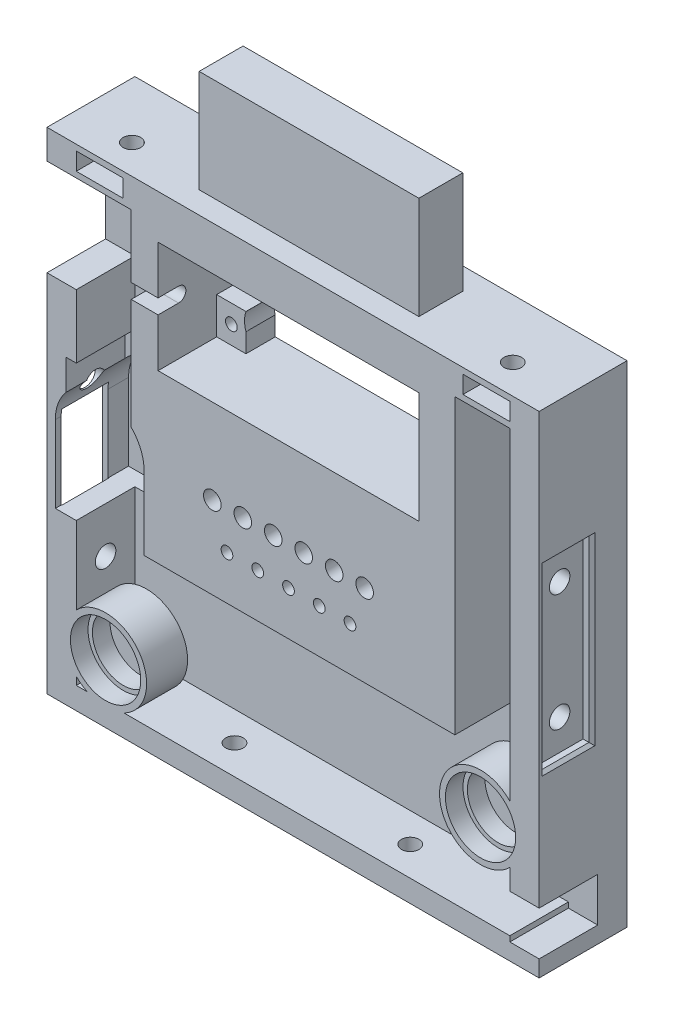
SolidWorks part; units mm, degrees
ref_plane "Front Plane" through (0, 0, 0) normal (0, 0, 1) x (1, 0, 0)
ref_plane "Top Plane" through (0, 0, 0) normal (0, 1, 0) x (1, 0, 0)
ref_plane "Right Plane" through (0, 0, 0) normal (1, 0, 0) x (0, 0, -1)
sketch "Sketch1" plane through (0, 0, 0) normal (0, 0, 1) x (1, 0, 0)
  line L1 (167.1854, 6.9235) -> (167.1854, 193.7719)
  line L2 (167.1854, 193.7719) -> (-0.8146, 193.7719)
  line L3 (-0.8146, 193.7719) -> (-0.8146, 6.9235)
  line L5 (81.6254, 98.7719) -> (102.6254, 98.7719) construction
  line L6 (83.1854, 270.7719) -> (99.1854, 270.7719) construction
  circle A0 centre (81.6254, 98.7719) radius 2
  circle A1 centre (102.6254, 98.7719) radius 2
  circle A2 centre (92.1254, 98.7719) radius 2
  circle A3 centre (60.6254, 98.7719) radius 2
  circle A4 centre (71.1254, 98.7719) radius 2
  arc A5 (83.1854, -1.2281) -> (167.1854, 6.9235) centre (99.1854, 270.7719) ccw
  arc A6 (83.1854, -1.2281) -> (-0.8146, 6.9235) centre (67.1854, 270.7719) cw
  dimension "D3" = 4
  dimension "D4" = 4
  dimension "D5" = 4
  dimension "D2" = 10.5
  dimension "D6" = 21
  dimension "D7" = 95
  dimension "D8" = 10.5
  dimension "D9" = 10.5
  dimension "D10" = 16
  dimension "D11" = 168
  dimension "D12" = 10.5
  dimension "D13" = 195
  dimension "D14" = 82.44
extrude "Boss-Extrude1" add sketch "Sketch1" along normal blind 30
sketch "Sketch2" plane through (0, 0, 30) normal (0, 0, 1) x (1, 0, 0)
  line L0 (107.1254, 178.7719) -> (56.1254, 178.7719)
  line L1 (81.6254, 58.2567) -> (81.6254, 96.2567) construction
  line L2 (56.1254, 140.7719) -> (107.1254, 140.7719)
  line L3 (-0.8146, 193.7719) -> (-0.8146, 6.9235) construction
  line L4 (167.1854, 193.7719) -> (-0.8146, 193.7719) construction
  line L10 (116.6254, 159.7719) -> (121.1254, 159.7719) construction
  line L12 (56.1254, 178.7719) -> (56.1254, 169.2719) construction
  line L13 (56.1254, 169.2719) -> (46.6254, 169.2719) construction
  line L14 (56.1254, 159.7719) -> (72.2173, 159.7719) construction
  line L15 (42.1254, 159.7719) -> (42.1254, 172.5219) construction
  line L16 (81.6254, 178.7719) -> (81.6254, 140.7719) construction
  circle A0 centre (42.1254, 172.5219) radius 2
  circle A1 centre (121.1254, 159.7719) radius 2
  circle A2 centre (42.1254, 159.7719) radius 2
  arc A4 (56.1254, 140.7719) -> (56.1254, 159.7719) centre (56.1254, 150.2719) cw
  arc A5 (107.1254, 178.7719) -> (107.1254, 159.7719) centre (107.1254, 169.2719) cw
  arc A6 (107.1254, 140.7719) -> (107.1254, 159.7719) centre (107.1254, 150.2719) ccw
  arc A7 (56.1254, 178.7719) -> (56.1254, 159.7719) centre (56.1254, 169.2719) ccw
  circle A8 centre (42.1254, 147.0219) radius 2
  circle A9 centre (121.1254, 147.0219) radius 2
  circle A10 centre (121.1254, 172.5219) radius 2
  dimension "D6" = 4
  dimension "D11" = 39.5
  dimension "D1" = 0
  dimension "D2" = 38
  dimension "D3" = 82.44
  dimension "D4" = 51
  dimension "D5" = 4.5
  dimension "D7" = 15
  dimension "D8" = 9.5
  dimension "D9" = 9.5
  dimension "D10" = 12.75
extrude "Cut-Extrude1" cut sketch "Sketch2" against normal through all both and the other way through all
sketch "Sketch3" plane through (0, 193.7719, 0) normal (0, 1, 0) x (1, 0, 0)
  line L0 (83.1854, 0) -> (83.1854, -7.5) construction
  line L1 (-0.8146, -30) -> (-0.8146, 0) construction
  line L3 (167.1854, 0) -> (-0.8146, 0) construction
  line L4 (83.1854, -7.5) -> (118.6254, -7.5) construction
  line L5 (118.6254, -7.5) -> (118.6254, -22.5) construction
  line L6 (118.6254, -22.5) -> (43.6254, -22.5) construction
  line L7 (43.6254, -22.5) -> (43.6254, -7.5) construction
  line L8 (43.6254, -7.5) -> (83.1854, -7.5) construction
  line L9 (118.6254, -7.5) -> (43.6254, -7.5)
  line L10 (43.6254, -7.5) -> (43.6254, -22.5)
  line L11 (43.6254, -22.5) -> (118.6254, -22.5)
  line L12 (118.6254, -22.5) -> (118.6254, -7.5)
  dimension "D1" = 75
  dimension "D2" = 44.44
  dimension "D3" = 7.5
extrude "Boss-Extrude2" add sketch "Sketch3" along normal blind 35
sketch "Sketch5" plane through (0, 0, 0) normal (0, 0, -1) x (-1, 0, 0)
  circle A0 centre (-42.1254, 159.7719) radius 4.375
  circle A1 centre (-121.1254, 159.7719) radius 4.375
  dimension "D1" = 8.75
  dimension "D2" = 8.75
extrude "Cut-Extrude4" cut sketch "Sketch5" against normal blind 2
sketch "Sketch6" plane through (0, 0, 0) normal (0, 0, -1) x (-1, 0, 0)
  line L0 (-60.6254, 98.7719) -> (-60.6254, 111.7719) construction
  line L1 (-60.6254, 111.7719) -> (0.8146, 111.7719) construction
  line L2 (0.8146, 193.7719) -> (0.8146, 6.9235) construction
  line L4 (0.8146, 111.7719) -> (-55.6254, 111.7719) construction
  line L5 (-167.1854, 6.9235) -> (-167.1854, 193.7719) construction
  circle A0 centre (-55.6254, 111.7719) radius 3
  circle A1 centre (-66.0254, 111.7719) radius 3
  circle A2 centre (-76.4254, 111.7719) radius 3
  circle A3 centre (-86.8254, 111.7719) radius 3
  circle A4 centre (-97.2254, 111.7719) radius 3
  circle A5 centre (-107.6254, 111.7719) radius 3
  dimension "D3" = 6
  dimension "D5" = 6
  dimension "D2" = 5
  dimension "D4" = 59.56
  dimension "D6" = 13
  dimension "D7" = 52
extrude "Cut-Extrude5" cut sketch "Sketch6" against normal through all
sketch "Sketch7" plane through (0, 0, 30) normal (0, 0, 1) x (1, 0, 0)
  line L0 (46.6254, 169.2719) -> (46.9367, 169.2719) construction
  line L6 (81.6254, 183.7719) -> (81.6254, 145.7719) construction
  line L8 (-0.8146, 193.7719) -> (-0.8146, 6.9235) construction
  line L15 (57.6854, 159.7719) -> (37.1047, 159.7719) construction
  line L17 (37.1047, 166.2719) -> (37.1047, 159.7719)
  line L18 (47.1047, 166.2719) -> (37.1047, 166.2719)
  line L22 (37.1047, 159.7719) -> (37.1047, 153.2719)
  line L24 (47.1047, 166.2719) -> (47.1047, 178.7719)
  line L25 (47.1047, 178.7719) -> (116.1461, 178.7719)
  line L27 (46.6254, 150.2719) -> (46.9367, 150.2719) construction
  line L29 (47.1047, 140.7719) -> (116.1461, 140.7719)
  line L30 (47.1047, 153.2719) -> (47.1047, 140.7719)
  line L31 (47.1047, 153.2719) -> (37.1047, 153.2719)
  line L32 (116.6254, 150.2719) -> (116.3141, 150.2719) construction
  line L33 (105.5654, 159.7719) -> (126.1461, 159.7719) construction
  line L34 (116.6254, 169.2719) -> (116.3141, 169.2719) construction
  line L35 (116.1461, 153.2719) -> (126.1461, 153.2719)
  line L36 (116.1461, 153.2719) -> (116.1461, 140.7719)
  line L39 (116.1461, 166.2719) -> (116.1461, 178.7719)
  line L40 (126.1461, 159.7719) -> (126.1461, 153.2719)
  line L41 (116.1461, 166.2719) -> (126.1461, 166.2719)
  line L42 (126.1461, 166.2719) -> (126.1461, 159.7719)
  line L43 (107.1254, 178.7719) -> (56.1254, 178.7719) construction
  line L44 (56.1254, 140.7719) -> (107.1254, 140.7719) construction
  arc A0 (56.1254, 178.7719) -> (56.1254, 159.7719) centre (56.1254, 169.2719) ccw construction
  point P33 (81.6254, 140.7719)
  point P35 (81.6254, 178.7719)
  dimension "D1" = 0
  dimension "D2" = 0
  dimension "D3" = 0
  dimension "D4" = 82.44
  dimension "D6" = 10
  dimension "D7" = 6.5
extrude "Cut-Extrude6" cut sketch "Sketch7" against normal through all and the other way through all
ref_plane "Plane1" through (0, 159.7719, 0) normal (0, 1, 0) x (1, 0, 0)
ref_plane "Plane2" through (81.6254, 0, 0) normal (-1, 0, 0) x (0, 0, 1)
mirror "Mirror2" about plane through (81.6254, 0, 0) normal (-1, 0, 0) rebuild error yes
sketch "Sketch9" plane through (167.1854, 0, 0) normal (1, 0, 0) x (0, 0, -1)
  line L1 (-30, 6.9235) -> (0, 6.9235) construction
  line L7 (-30, 6.9235) -> (-30, 193.7719) construction
  circle A0 centre (-20, 136.9235) radius 3.5
  circle A1 centre (-20, 96.9235) radius 3.5
  dimension "D5" = 40
  dimension "D6" = 10
  dimension "D7" = 90
sketch "Sketch10" plane through (-0.8146, 0, 0) normal (-1, 0, 0) x (0, 0, 1)
  line L0 (30, 6.9235) -> (0, 6.9235) construction
  line L7 (30, 193.7719) -> (30, 6.9235) construction
  circle A0 centre (20, 116.9235) radius 3.5
  circle A1 centre (20, 66.9235) radius 3.5
  dimension "D5" = 10
  dimension "D6" = 50
  dimension "D1" = 60
sketch "Sketch11" plane through (0, 0, 30) normal (0, 0, 1) x (1, 0, 0)
  line L0 (37.1047, 159.7719) -> (-0.8146, 159.7719) construction
  line L1 (37.1047, 153.2719) -> (37.1047, 166.2719) construction
  line L2 (-0.8146, 193.7719) -> (-0.8146, 6.9235) construction
  line L3 (-0.8146, 159.7719) -> (9.1854, 159.7719) construction
  line L4 (9.1854, 159.7719) -> (27.9354, 159.7719) construction
  line L14 (167.1854, 159.7719) -> (157.1854, 159.7719) construction
  line L15 (128.4341, 159.7719) -> (138.4354, 159.7719) construction
  line L21 (47.1047, 140.7719) -> (27.9354, 140.7719) construction
  line L22 (27.9354, 140.7719) -> (27.9354, 128.6081) construction
  line L24 (27.9354, 128.6081) -> (27.9354, 83.7719)
  line L30 (167.1854, 6.9235) -> (167.1854, 46.9235) construction
  line L31 (27.9354, 183.7719) -> (27.9354, 128.6081)
  line L32 (39.2538, 83.7719) -> (138.4354, 83.7719)
  line L33 (157.1854, 183.7719) -> (9.1854, 183.7719)
  line L34 (9.1854, 183.7719) -> (9.1854, 14.7903)
  line L35 (157.1854, 14.7903) -> (157.1854, 183.7719)
  line L37 (9.1854, 183.7719) -> (9.1854, 128.6081)
  line L38 (157.1854, 14.7903) -> (157.1854, 18.7719)
  line L40 (27.9354, 183.7719) -> (9.1854, 183.7719)
  line L41 (167.1854, 6.9235) -> (167.1854, 193.7719) construction
  line L42 (167.1854, 46.9235) -> (157.1854, 46.9235) construction
  line L47 (138.4354, 183.7719) -> (138.4354, 159.7719)
  line L48 (157.1854, 183.7719) -> (157.1854, 159.7719)
  line L51 (157.1854, 159.7719) -> (167.1854, 159.7719) construction
  line L52 (138.4354, 183.7719) -> (157.1854, 183.7719)
  line L53 (9.1854, 128.6081) -> (9.1854, 33.7719)
  line L54 (9.1854, 14.7903) -> (27.9354, 11.2531)
  line L55 (138.4354, 159.7719) -> (138.4354, 83.7719)
  line L56 (157.1854, 159.7719) -> (157.1854, 46.9235)
  line L57 (27.9354, 83.7719) -> (39.2538, 83.7719)
  line L58 (9.1854, 18.7719) -> (157.1854, 18.7719)
  line L60 (157.1854, 33.7719) -> (9.1854, 33.7719)
  line L62 (43.6254, 228.7719) -> (118.6254, 228.7719) construction
  line L63 (9.1854, 18.7719) -> (9.1854, 14.7903)
  line L64 (157.1854, 33.7719) -> (157.1854, 46.9235)
  arc A8 (9.1854, 14.7903) -> (83.1854, 8.7899) centre (67.1854, 270.7719) ccw
  arc A9 (83.1854, 8.7899) -> (157.1854, 14.7903) centre (99.1854, 270.7719) ccw
  arc A10 (27.9354, 11.2531) -> (83.1854, 8.7899) centre (67.1854, 270.7719) ccw
  arc A11 (83.1854, 8.7899) -> (157.1854, 14.7903) centre (99.1854, 270.7719) ccw
  dimension "D1" = 10
  dimension "D2" = 210
  dimension "D3" = 15
  dimension "D4" = 50
extrude "Cut-Extrude8" cut sketch "Sketch11" against normal blind 20
sketch "Sketch19" plane through (0, 14.7903, 0) normal (0, 1, 0) x (0, 0, 1)
  line L0 (30, 9.1854) -> (20, 9.1854) construction
  line L1 (10, 9.1854) -> (30, 9.1854) construction
  line L2 (20, 9.1854) -> (20, 19.1854) construction
  line L4 (20, 19.1854) -> (20, 16.4354)
  line L7 (20, 16.4354) -> (17, 16.4354)
  line L8 (17, 16.4354) -> (17, 21.9354)
  line L9 (17, 21.9354) -> (20, 21.9354)
  line L10 (20, 21.9354) -> (20, 19.1854)
  dimension "D1" = 3
  dimension "D2" = 2.75
  dimension "D3" = 5.5
  dimension "D4" = 10
extrude "Cut-Extrude12" cut sketch "Sketch19" against normal blind 10.5
fillet "Fillet2" radius 7 2 edges at (40.8679, -0.4243, 0) (125.503, -0.4243, 0)
sketch "Sketch20" plane through (9.1854, 0, 0) normal (1, 0, 0) x (0, 0, -1)
  line L0 (-30, 183.7719) -> (-30, 150.7719)
  line L1 (-30, 183.7719) -> (-30, 33.7719) construction
  line L2 (-30, 150.7719) -> (-10, 150.7719)
  line L3 (-10, 183.7719) -> (-10, 33.7719) construction
  line L4 (-10, 150.7719) -> (-10, 183.7719)
  line L5 (-10, 183.7719) -> (-30, 183.7719)
extrude "Cut-Extrude13" cut sketch "Sketch20" against normal blind 10
ref_plane "Plane5" through (0, 0, 15) normal (0, 0, 1) x (1, 0, 0)
extrude "Cut-Extrude14" cut sketch "Sketch10" against normal blind 20
sketch "Sketch21" plane through (0, 0, 10) normal (0, 0, 1) x (1, 0, 0)
  line L0 (-0.8146, 150.7719) -> (-0.8146, 183.7719) construction
  line L3 (167.1854, 193.7719) -> (-0.8146, 193.7719) construction
  circle A0 centre (17.1854, 108.7719) radius 4.75
  dimension "D1" = 18
  dimension "D2" = 85
extrude "Cut-Extrude15" cut sketch "Sketch21" against normal blind 20
sketch "Sketch22" plane through (0, 0, 10) normal (0, 0, 1) x (1, 0, 0)
  line L0 (2.0278, 108.7719) -> (2.0278, 82.5219)
  line L1 (2.0278, 82.5219) -> (32.343, 82.5219)
  line L2 (32.343, 82.5219) -> (32.343, 108.7719)
  arc A0 (32.343, 108.7719) -> (2.0278, 108.7719) centre (17.1854, 108.7719) ccw
  dimension "D1" = 26.25
extrude "Cut-Extrude16" cut sketch "Sketch22" against normal blind 5
sketch "Sketch25" plane through (37.1047, 0, 0) normal (1, 0, 0) x (0, 0, -1)
  line L0 (-30, 153.2719) -> (-30, 159.7719) construction
  line L1 (-30, 153.2719) -> (-30, 166.2719) construction
  line L2 (-30, 159.7719) -> (-23, 159.7719) construction
  line L3 (-23, 157.2719) -> (-30, 157.2719)
  line L4 (-30, 157.2719) -> (-30, 162.2719)
  line L5 (-30, 162.2719) -> (-23, 162.2719)
  arc A0 (-23, 157.2719) -> (-23, 162.2719) centre (-23, 159.7719) ccw
extrude "Cut-Extrude19" cut sketch "Sketch25" against normal blind 15
extrude "Cut-Extrude20" cut sketch "Sketch9" against normal blind 25
sketch "Sketch26" plane through (157.1854, 0, 0) normal (-1, 0, 0) x (0, 0, 1)
  line L0 (30, 46.9235) -> (10, 46.9235)
  line L1 (10, 46.9235) -> (10, 31.9235)
  line L2 (10, 14.7903) -> (10, 18.7719) construction
  line L3 (10, 31.9235) -> (30, 31.9235)
  line L4 (30, 14.7903) -> (30, 18.7719) construction
  line L5 (30, 31.9235) -> (30, 46.9235)
  dimension "D1" = 15
extrude "Cut-Extrude21" cut sketch "Sketch26" against normal blind 25
ref_plane "Plane4" through (83.1854, 0, 0) normal (-1, 0, 0) x (0, 0, 1)
mirror "Mirror9" about plane through (83.1854, 0, 0) normal (-1, 0, 0) of "Cut-Extrude12"
ref_plane "Plane6" through (0, -1.2281, 0) normal (0, -1, 0) x (-1, 0, 0)
sketch "Sketch27" plane through (0, -1.2281, 0) normal (0, -1, 0) x (-1, 0, 0)
  line L0 (-83.1854, -30) -> (-83.1854, -20) construction
  line L1 (-83.1854, -30) -> (-83.1854, -7) construction
  circle A0 centre (-83.1854, -20) radius 6.5
extrude "Cut-Extrude23" cut sketch "Sketch27" along normal blind 2
sketch "Sketch28" plane through (0, -1.2281, 0) normal (0, -1, 0) x (1, 0, 0)
  line L0 (83.1854, 26.5) -> (83.1854, 13.5) construction
  circle A0 centre (83.1854, 20) radius 6.5
extrude "Cut-Extrude24" cut sketch "Sketch28" against normal blind 2
sketch "Sketch30" plane through (0, 0.7719, 0) normal (0, -1, 0) x (1, 0, 0)
  circle A0 centre (83.1854, 20) radius 2
extrude "Cut-Extrude25" cut sketch "Sketch30" against normal up to next
sketch "Sketch31" plane through (0, 33.7719, 0) normal (0, 1, 0) x (1, 0, 0)
  line L0 (83.1854, -30) -> (83.1854, -10) construction
  line L1 (9.1854, -30) -> (157.1854, -30) construction
  line L2 (9.1854, -10) -> (157.1854, -10) construction
  line L3 (83.1854, -10) -> (83.1854, -20) construction
  line L4 (83.1854, -20) -> (113.1854, -20) construction
  line L5 (113.1854, -20) -> (53.1854, -20) construction
  circle A0 centre (53.1854, -20) radius 3
  circle A1 centre (113.1854, -20) radius 3
  dimension "D1" = 30
  dimension "D2" = 60
extrude "Cut-Extrude26" cut sketch "Sketch31" against normal blind 15
sketch "Sketch32" plane through (0, 0, 30) normal (0, 0, 1) x (1, 0, 0)
  line L0 (83.1854, 33.7719) -> (83.1854, 26.2719) construction
  line L1 (9.1854, 33.7719) -> (157.1854, 33.7719) construction
  line L2 (83.1854, 26.2719) -> (-8.5825, 26.2719)
  line L3 (-8.5825, 26.2719) -> (-8.5825, -8.8315)
  line L4 (-8.5825, -8.8315) -> (175.9833, -8.8315)
  line L5 (175.9833, -8.8315) -> (175.9833, 26.2719)
  line L6 (175.9833, 26.2719) -> (83.1854, 26.2719)
extrude "Cut-Extrude27" cut sketch "Sketch32" against normal blind 30
sketch "Sketch33" plane through (167.1854, 0, 0) normal (1, 0, 0) x (0, 0, -1)
  line L0 (-20, 136.9235) -> (-20, 147.4235) construction
  line L1 (-20, 147.4235) -> (-12, 147.4235) construction
  line L2 (-20, 96.9235) -> (-20, 86.4235) construction
  line L3 (-20, 86.4235) -> (-28, 86.4235) construction
  line L4 (-12, 147.4235) -> (-12, 86.4235)
  line L5 (-12, 86.4235) -> (-28, 86.4235)
  line L6 (-28, 86.4235) -> (-28, 147.4235)
  line L7 (-28, 147.4235) -> (-12, 147.4235)
  dimension "D1" = 8
  dimension "D2" = 10.5
  dimension "D3" = 10.5
  dimension "D4" = 8
extrude "Cut-Extrude28" cut sketch "Sketch33" against normal blind 3
sketch "Sketch34" plane through (0, 26.2719, 0) normal (0, -1, 0) x (1, 0, 0)
  line L0 (113.1854, 20) -> (123.6854, 20) construction
  line L1 (123.6854, 20) -> (123.6854, 12) construction
  line L2 (53.1854, 20) -> (42.6854, 20) construction
  line L3 (42.6854, 20) -> (42.6854, 28) construction
  line L4 (123.6854, 12) -> (42.6854, 12)
  line L5 (42.6854, 12) -> (42.6854, 28)
  line L6 (42.6854, 28) -> (123.6854, 28)
  line L7 (123.6854, 28) -> (123.6854, 12)
extrude "Cut-Extrude29" cut sketch "Sketch34" against normal blind 3
sketch "Sketch35" plane through (-0.8146, 0, 0) normal (-1, 0, 0) x (0, 0, 1)
  line L0 (20, 66.9235) -> (20, 56.4235) construction
  line L1 (20, 56.4235) -> (12, 56.4235) construction
  line L2 (20, 116.9235) -> (20, 127.4235) construction
  line L3 (20, 127.4235) -> (28, 127.4235) construction
  line L4 (12, 56.4235) -> (12, 127.4235)
  line L5 (12, 127.4235) -> (28, 127.4235)
  line L6 (28, 127.4235) -> (28, 56.4235)
  line L7 (28, 56.4235) -> (12, 56.4235)
  dimension "D1" = 10.5
  dimension "D2" = 8
extrude "Cut-Extrude30" cut sketch "Sketch35" against normal blind 3
chamfer "Chamfer3" distance 1 angle 45 12 edges at (167.1854, 86.4235, 20) (167.1854, 116.9235, 12) (167.1854, 116.9235, 28) (167.1854, 147.4235, 20) (42.6854, 26.2719, 20) (83.1854, 26.2719, 12) (123.6854, 26.2719, 20) (83.1854, 26.2719, 28) (-0.8146, 91.9235, 28) (-0.8146, 127.4235, 20) (-0.8146, 56.4235, 20) (-0.8146, 91.9235, 12)
sketch "Sketch36" plane through (0, 183.7719, 0) normal (0, -1, 0) x (1, 0, 0)
  line L0 (157.1854, 30) -> (148.1854, 30) construction
  line L1 (157.1854, 30) -> (138.4354, 30) construction
  line L2 (148.1854, 30) -> (148.1854, 20) construction
  line L3 (-0.8146, 30) -> (18.1854, 30) construction
  line L4 (27.9354, 30) -> (-0.8146, 30) construction
  line L5 (18.1854, 30) -> (18.1854, 20) construction
  circle A0 centre (148.1854, 20) radius 3
  circle A1 centre (18.1854, 20) radius 3
  dimension "D2" = 10
  dimension "D1" = 10
extrude "Cut-Extrude31" cut sketch "Sketch36" against normal up to next
sketch "Sketch37" plane through (0, 0, 5) normal (0, 0, 1) x (1, 0, 0)
  line L3 (2.0278, 108.7719) -> (2.0278, 82.5219)
  line L4 (2.0278, 82.5219) -> (32.343, 82.5219)
  line L5 (32.343, 82.5219) -> (32.343, 108.7719)
  line L6 (2.0278, 108.7719) -> (2.0278, 82.5219)
  line L7 (2.0278, 82.5219) -> (32.343, 82.5219)
  line L8 (32.343, 82.5219) -> (32.343, 108.7719)
  arc A1 (32.343, 108.7719) -> (2.0278, 108.7719) centre (17.1854, 108.7719) ccw
  arc A2 (32.343, 108.7719) -> (2.0278, 108.7719) centre (17.1854, 108.7719) ccw
  dimension "D1" = 0
extrude "Cut-Extrude32" cut sketch "Sketch37" along normal up to surface (25 mm away) up to face at (83.1854, 60.6848, 30)
sketch "Sketch38" plane through (0, 0, 30) normal (0, 0, 1) x (1, 0, 0)
  line L0 (37.1047, 166.2719) -> (37.1047, 178.7719)
  line L1 (37.1047, 178.7719) -> (116.1461, 178.7719)
  line L2 (116.1461, 178.7719) -> (126.1461, 178.7719)
  line L3 (126.1461, 178.7719) -> (126.1461, 140.7719)
  line L4 (126.1461, 140.7719) -> (37.1047, 140.7719)
  line L5 (37.1047, 140.7719) -> (37.1047, 166.2719)
extrude "Cut-Extrude33" cut sketch "Sketch38" against normal blind 20
sketch "Sketch39" plane through (0, 0, 30) normal (0, 0, 1) x (1, 0, 0)
  line L0 (-0.8146, 26.2719) -> (19.1854, 26.2719) construction
  line L1 (167.1854, 26.2719) -> (-0.8146, 26.2719) construction
  line L2 (19.1854, 26.2719) -> (19.1854, 46.2719) construction
  circle A0 centre (19.1854, 46.2719) radius 14
  dimension "D1" = 20
  dimension "D3" = 28
  dimension "D2" = 20
extrude "Boss-Extrude3" add sketch "Sketch39" against normal blind 14 contours A0
sketch "Sketch41" plane through (0, 0, 30) normal (0, 0, 1) x (1, 0, 0)
  line L0 (19.1854, 60.2719) -> (19.1854, 46.2719) construction
  arc A0 (25.4902, 33.7719) -> (9.1854, 56.0699) centre (19.1854, 46.2719) ccw construction
  circle A1 centre (19.1854, 46.2719) radius 12
extrude "Cut-Extrude34" cut sketch "Sketch41" against normal blind 6
sketch "Sketch42" plane through (0, 0, 24) normal (0, 0, 1) x (1, 0, 0)
  line L0 (12.1765, 56.0123) -> (19.1854, 46.2719) construction
  circle A0 centre (19.1854, 46.2719) radius 12 construction
  circle A1 centre (19.1854, 46.2719) radius 10.5
extrude "Cut-Extrude35" cut sketch "Sketch42" against normal blind 6
sketch "Sketch43" plane through (0, 0, 30) normal (0, 0, 1) x (1, 0, 0)
  line L0 (167.1854, 46.9235) -> (167.1854, 63.7719) construction
  line L1 (167.1854, 46.9235) -> (167.1854, 193.7719) construction
  line L2 (167.1854, 63.7719) -> (147.1854, 63.7719) construction
  line L3 (167.1854, 193.7719) -> (-0.8146, 193.7719) construction
  circle A0 centre (147.1854, 63.7719) radius 14
  dimension "D1" = 130
  dimension "D2" = 20
extrude "Boss-Extrude4" add sketch "Sketch43" against normal blind 14
sketch "Sketch44" plane through (0, 0, 30) normal (0, 0, 1) x (1, 0, 0)
  line L0 (136.3396, 72.6246) -> (147.1854, 63.7719) construction
  arc A0 (157.1854, 73.5699) -> (157.1854, 53.974) centre (147.1854, 63.7719) ccw construction
  circle A1 centre (147.1854, 63.7719) radius 12
extrude "Cut-Extrude36" cut sketch "Sketch44" against normal blind 6 contours A1
sketch "Sketch45" plane through (0, 0, 24) normal (0, 0, 1) x (1, 0, 0)
  line L0 (138.3545, 71.8969) -> (147.1854, 63.7719) construction
  circle A0 centre (147.1854, 63.7719) radius 12 construction
  circle A1 centre (147.1854, 63.7719) radius 10.5
sketch "Sketch46" plane through (0, 0, 30) normal (0, 0, 1) x (1, 0, 0)
  line L0 (-0.8146, 193.7719) -> (9.1854, 193.7719) construction
  line L1 (167.1854, 193.7719) -> (-0.8146, 193.7719) construction
  line L2 (9.1854, 193.7719) -> (9.1854, 191.7719) construction
  line L3 (9.1854, 191.7719) -> (25.1854, 191.7719)
  line L4 (25.1854, 191.7719) -> (25.1854, 185.7719)
  line L5 (25.1854, 185.7719) -> (9.1854, 185.7719)
  line L6 (9.1854, 185.7719) -> (9.1854, 191.7719)
  line L7 (167.1854, 193.7719) -> (157.1854, 193.7719) construction
  line L8 (157.1854, 193.7719) -> (157.1854, 191.7719) construction
  line L9 (157.1854, 191.7719) -> (157.1854, 185.7719)
  line L10 (157.1854, 185.7719) -> (141.1854, 185.7719)
  line L11 (141.1854, 185.7719) -> (141.1854, 191.7719)
  line L12 (141.1854, 191.7719) -> (157.1854, 191.7719)
  line L13 (167.1854, 26.2719) -> (-0.8146, 26.2719) construction
  dimension "D1" = 10
  dimension "D2" = 2
  dimension "D3" = 16
  dimension "D4" = 167.5
extrude "Cut-Extrude37" cut sketch "Sketch46" against normal blind 6
extrude "Cut-Extrude38" cut sketch "Sketch45" against normal blind 6 contours A1
sketch "Sketch47" plane through (0, 0, 30) normal (0, 0, 1) x (1, 0, 0)
  line L0 (5.7408, 129.0464) -> (5.7408, 113.5535)
  line L1 (5.7408, 129.0464) -> (9.1854, 129.0464)
  line L2 (9.1854, 150.7719) -> (9.1854, 121.6464) construction
  line L3 (5.7408, 113.5535) -> (9.1854, 113.5535)
  line L4 (9.1854, 113.5535) -> (9.1854, 129.0464)
extrude "Cut-Extrude39" cut sketch "Sketch47" against normal blind 20 contours L4 L1 L0 L3
